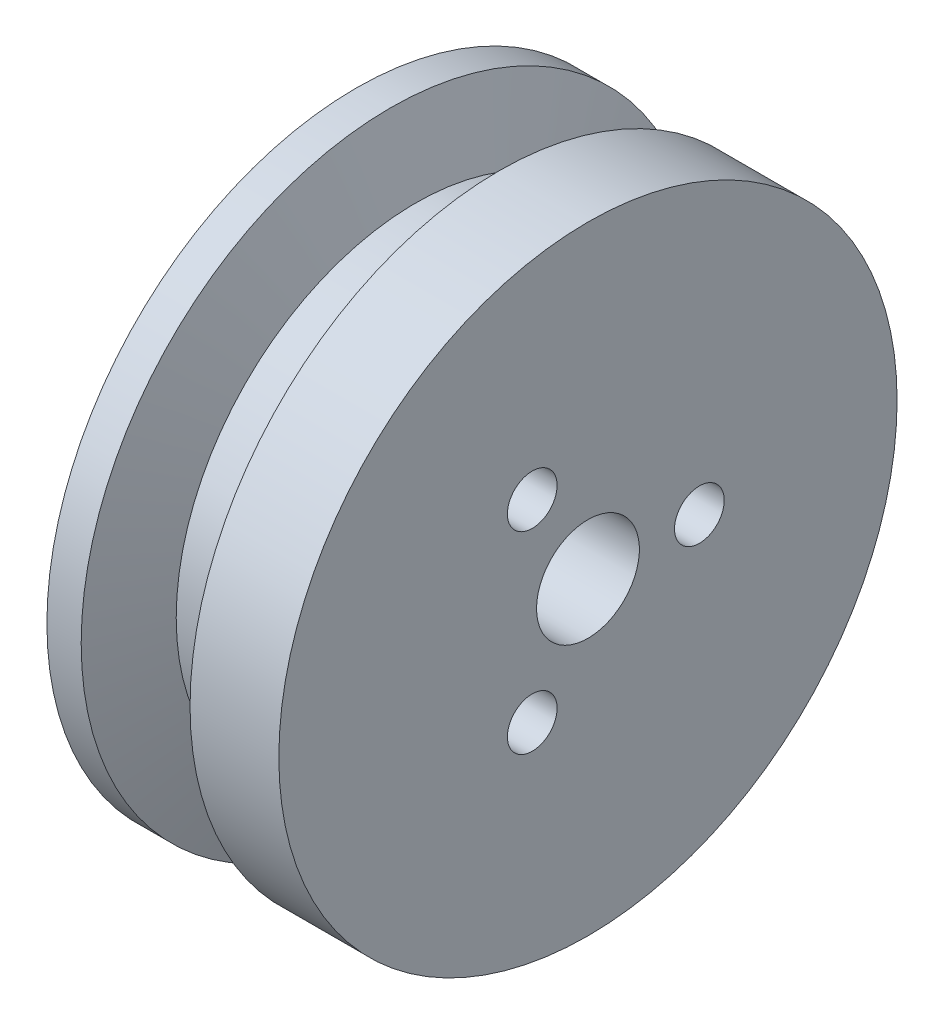
SolidWorks part; units mm, degrees
ref_plane "Front" through (0, 0, 0) normal (0, 0, 1) x (1, 0, 0)
ref_plane "Top" through (0, 0, 0) normal (0, 1, 0) x (1, 0, 0)
ref_plane "Right" through (0, 0, 0) normal (1, 0, 0) x (0, 0, -1)
sketch "Sketch1" plane through (0, 0, 0) normal (0, 0, 1) x (1, 0, 0)
  line L0 (0, 0) -> (11.2549, 0) construction
  line L1 (0, 0) -> (0, 18.034)
  line L2 (0, 18.034) -> (2, 18.034)
  line L3 (2, 18.034) -> (3.4792, 13.97)
  line L4 (3.4792, 13.97) -> (6.8708, 13.97)
  line L5 (8.35, 18.034) -> (13.53, 18.034)
  line L6 (6.8708, 13.97) -> (8.35, 18.034)
  line L7 (13.53, 18.034) -> (13.53, 3)
  line L8 (8.53, 3) -> (13.53, 3)
  line L9 (5.175, 13.97) -> (5.175, 3) construction
  line L11 (0, 0) -> (8.53, 0)
  line L12 (8.53, 0) -> (8.53, 3)
  dimension "D1" = 6.35
  dimension "D2" = 40
  dimension "D3" = 6
  dimension "D4" = 5
  dimension "D5" = 5.18
  dimension "D6" = 36.068
  dimension "D7" = 2
  dimension "D8" = 4.064
revolve "Revolve1" add sketch "Sketch1" angle 360 about L0
sketch "Sketch2" plane through (0, 0, 0) normal (-1, 0, 0) x (0, 0, 1)
  circle A0 centre (0, 0) radius 6.5 construction
  dimension "D1" = 13
hole_wizard "CBORE for M2.5 SHCS1" positions "Sketch5" profile "Sketch6" counterbore size "M2.5" standard "ANSI Metric" end condition through all
sketch "Sketch5" plane through (0, 0, 0) normal (-1, 0, 0) x (0, 0, 1)
  circle A0 centre (0, 0) radius 6.5 construction
  point P0 (-6.5, 0)
  point P8 (3.25, 5.6292)
  point P9 (3.25, -5.6292)
  dimension "D1" = 3
sketch "Sketch6" plane through (0, 0, -6.5) normal (0, 1, 0) x (0, 0, 1)
  line L0 (0, 0) -> (0, 13.53)
  line L1 (0, 13.53) -> (1.45, 13.53)
  line L3 (1.45, 13.53) -> (1.45, 9)
  line L4 (1.45, 9) -> (2.75, 9)
  line L5 (2.75, 9) -> (2.75, 0)
  line L7 (2.75, 0) -> (0, 0)
  line L11 (0, -6.35) -> (0, 107.95) construction
  dimension "Thru Hole Dia." = 2.9
  dimension "Thru Hole Depth" = 13.53
  dimension "C'Bore Dia." = 5.5
  dimension "C'Bore Depth" = 9
hole_wizard "#10-32 Tapped Hole1" positions "Sketch7" profile "Sketch9" tap size "#10-32" standard "ANSI Inch" end condition through all
sketch "Sketch7" plane through (0, 0, 0) normal (-1, 0, 0) x (0, 0, 1)
  point P0 (0, 0)
sketch "Sketch9" plane through (0, 0, 0) normal (0, 1, 0) x (0, 0, 1)
  line L0 (0, 0) -> (0, 13.53)
  line L1 (0, 13.53) -> (2.0193, 13.53)
  line L2 (2.0193, 13.53) -> (2.0193, 0)
  line L5 (2.0193, 0) -> (0, 0)
  line L11 (0, -6.35) -> (0, 107.95) construction
  dimension "Thru Tap Drill Dia." = 4.0386
  dimension "Thru Tap Drill Depth" = 13.53
cosmetic thread "Hole Thread1" parameters "D2"=4.826
ref_plane "Plane1" through (5.175, 0, 0) normal (-1, 0, 0) x (0, 0, 1)
